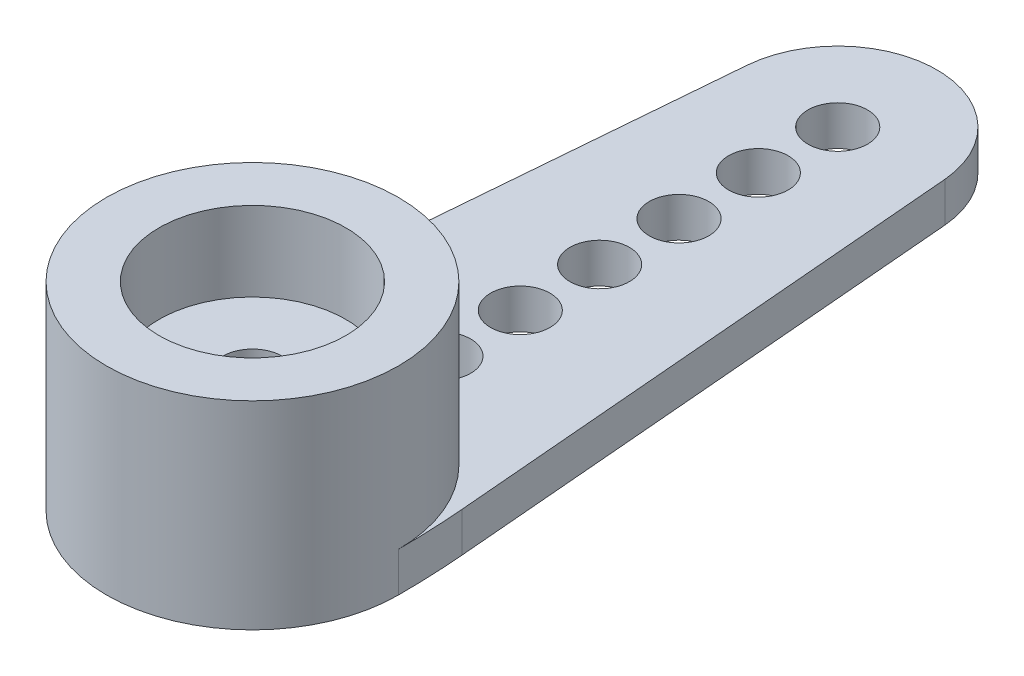
SolidWorks part; units mm, degrees
material "ABS"
ref_plane "Front Plane" through (0, 0, 0) normal (0, 0, 1) x (1, 0, 0)
ref_plane "Top Plane" through (0, 0, 0) normal (0, 1, 0) x (1, 0, 0)
ref_plane "Right Plane" through (0, 0, 0) normal (1, 0, 0) x (0, 0, -1)
sketch "Sketch1" plane through (0, 0, 0) normal (0, 1, 0) x (1, 0, 0)
  line L0 (0, -14.75) -> (0, 14.75) construction
  line L1 (-2.5, -14.75) -> (-2.5, 14.75) construction
  line L2 (2.5, -14.75) -> (2.5, 14.75) construction
  line L3 (-2.4912, 14.9596) -> (-3.6089, 1.677)
  line L4 (-3.6089, -1.677) -> (-2.4912, -14.9596)
  line L5 (0, 0) -> (0, -19.6174) construction
  line L6 (3.6089, -1.677) -> (2.4912, -14.9596)
  line L7 (2.4912, 14.9596) -> (3.6089, 1.677)
  line L8 (0, 0) -> (20.4602, 0) construction
  arc A0 (-2.5, -14.75) -> (2.5, -14.75) centre (0, -14.75) ccw construction
  arc A1 (2.5, 14.75) -> (-2.5, 14.75) centre (0, 14.75) ccw construction
  arc A2 (-2.4912, 14.9596) -> (2.4912, 14.9596) centre (0, 14.75) cw
  arc A3 (-2.4912, -14.9596) -> (2.4912, -14.9596) centre (0, -14.75) ccw
  circle A4 centre (0, 14.75) radius 0.75
  arc A5 (3.6089, -1.677) -> (3.6089, 1.677) centre (-16.3207, 0) ccw
  arc A6 (-3.6089, 1.677) -> (-3.6089, -1.677) centre (16.3207, 0) ccw
  circle A7 centre (0, 0) radius 3.6793
  circle A8 centre (0, 12.75) radius 0.75
  circle A9 centre (0, 10.75) radius 0.75
  circle A10 centre (0, 8.75) radius 0.75
  circle A11 centre (0, 6.75) radius 0.75
  circle A12 centre (0, 4.75) radius 0.75
  circle A13 centre (0, 0) radius 0.75
  circle A14 centre (0, -4.75) radius 0.75
  circle A15 centre (0, -6.75) radius 0.75
  circle A16 centre (0, -8.75) radius 0.75
  circle A17 centre (0, -10.75) radius 0.75
  circle A18 centre (0, -12.75) radius 0.75
  circle A19 centre (0, -14.75) radius 0.75
  point P2 (0, 0)
  point P21 (3.75, 0)
  point P24 (-3.75, 0)
  dimension "D1" = 2.5
  dimension "D4" = 1.5
  dimension "D5" = 20
  dimension "D2" = 29.5
  dimension "D3" = 3.75
  dimension "D7" = 2
  dimension "D6" = 6
extrude "Boss-Extrude1" add sketch "Sketch1" along normal blind 1 contours A7 A13 | A7 A5 L7 A2 L3 A6 A12 A11 A10 A9 A8 A4 region at (0, 0, -17.0625) region at (0, 0, -3.5753)
sketch "Sketch2" plane through (0, 0, 0) normal (0, -1, 0) x (1, 0, 0)
  circle A0 centre (0, 0) radius 3.6793 construction
  circle A1 centre (0, 0) radius 3.6793
  circle A2 centre (0, 0) radius 1.5
  dimension "D1" = 3
extrude "Boss-Extrude2" add sketch "Sketch2" against normal blind 5 contours A1
extrude "Cut-Extrude1" cut sketch "Sketch2<3>" against normal blind 0.5 contours A2
sketch "Sketch2<3>" plane through (0, 0, 0) normal (0, -1, 0) x (1, 0, 0) same geometry as "Sketch2"
extrude "Cut-Extrude2" cut sketch "Sketch1<2>" along normal through all contours A13
sketch "Sketch1<2>" plane through (0, 0, 0) normal (0, 1, 0) x (1, 0, 0) same geometry as "Sketch1"
sketch "Sketch3" plane through (0, 5, 0) normal (0, 1, 0) x (1, 0, 0)
  circle A0 centre (0, 0) radius 2.355
  dimension "D1" = 4.71
extrude "Cut-Extrude3" cut sketch "Sketch3" against normal blind 2
